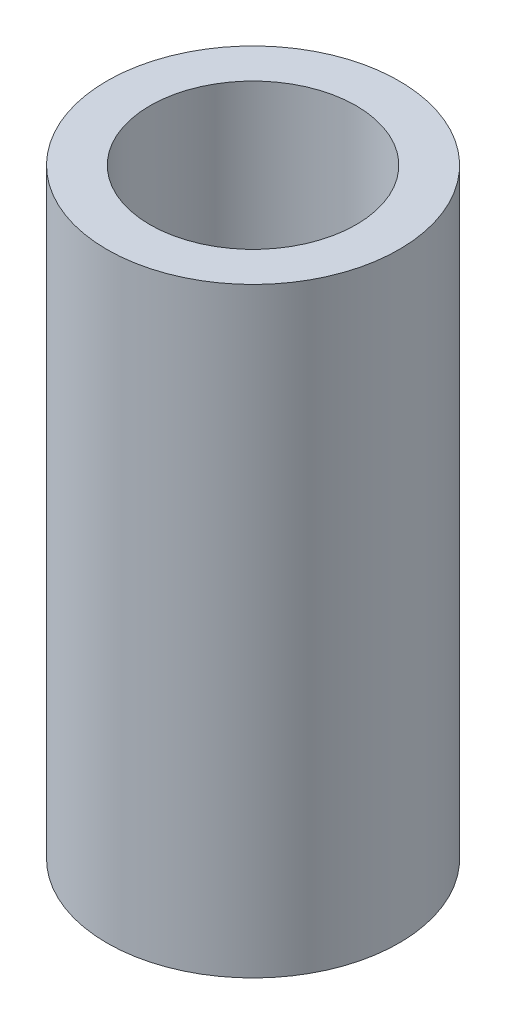
SolidWorks part; units mm, degrees
material "ABS"
ref_plane "Front Plane" through (0, 0, 0) normal (0, 0, 1) x (1, 0, 0)
ref_plane "Top Plane" through (0, 0, 0) normal (0, 1, 0) x (1, 0, 0)
ref_plane "Right Plane" through (0, 0, 0) normal (1, 0, 0) x (0, 0, -1)
sketch "Sketch1" plane through (0, 0, 0) normal (0, 1, 0) x (1, 0, 0)
  circle A0 centre (0, 0) radius 24
  circle A1 centre (0, 0) radius 34
  dimension "D1" = 48
  dimension "D2" = 68
extrude "Boss-Extrude1" add sketch "Sketch1" along normal blind 139.8
sketch "Sketch2" plane through (0, 0, 0) normal (1, 0, 0) x (0, 0, -1)
  line L1 (34, 139.8) -> (-34, 139.8) construction
  circle A0 centre (0, 22.6) radius 12.53
  circle A1 centre (0, 75.6) radius 12.53
  dimension "D1" = 25.06
  dimension "D2" = 25.06
  dimension "D3" = 64.2
  dimension "D5" = 53
extrude "Cut-Extrude1" cut sketch "Sketch2" against normal through all
